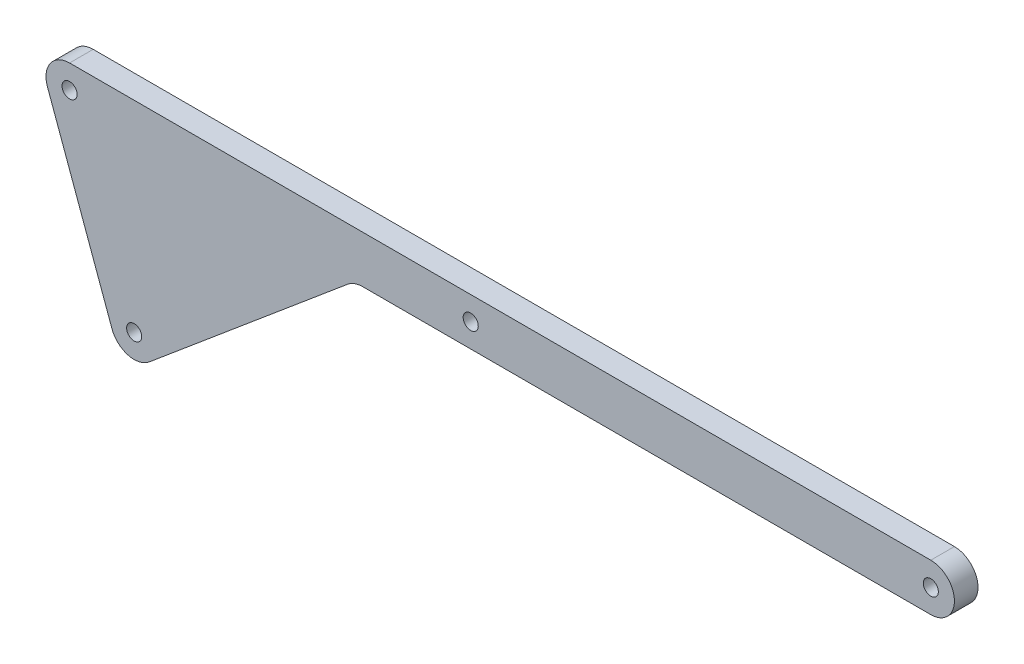
SolidWorks part; units mm, degrees
ref_plane "Front Plane" through (0, 0, 0) normal (0, 0, 1) x (1, 0, 0)
ref_plane "Top Plane" through (0, 0, 0) normal (0, 1, 0) x (1, 0, 0)
ref_plane "Right Plane" through (0, 0, 0) normal (1, 0, 0) x (0, 0, -1)
sketch "Sketch2" plane through (0, 0, 0) normal (0, 0, 1) x (1, 0, 0)
  line L1 (0, 6.35) -> (231.775, 6.35)
  line L2 (78.8871, -6.35) -> (231.775, -6.35)
  line L3 (-5.967, -2.1718) -> (11.4076, -49.9082)
  line L4 (21.4563, -52.6008) -> (74.8054, -7.8356)
  arc A0 (0, 6.35) -> (-5.967, -2.1718) centre (0, 0) ccw
  arc A1 (231.775, -6.35) -> (231.775, 6.35) centre (231.775, 0) ccw
  circle A2 centre (0, 0) radius 2.032
  circle A3 centre (231.775, 0) radius 2.032
  circle A5 centre (107.95, 0) radius 2.032
  arc A6 (11.4076, -49.9082) -> (21.4563, -52.6008) centre (17.3746, -47.7364) ccw
  arc A7 (74.8054, -7.8356) -> (78.8871, -6.35) centre (78.8871, -12.7) cw
  circle A8 centre (17.3746, -47.7364) radius 2.032
  dimension "D3" = 4.064
  dimension "D4" = 50.8
  dimension "D5" = 70
  dimension "D6" = 107.95
  dimension "D7" = 70
  dimension "D1" = 231.775
  dimension "D2" = 12.7
extrude "Boss-Extrude1" add sketch "Sketch2" along normal mid plane 6.35
